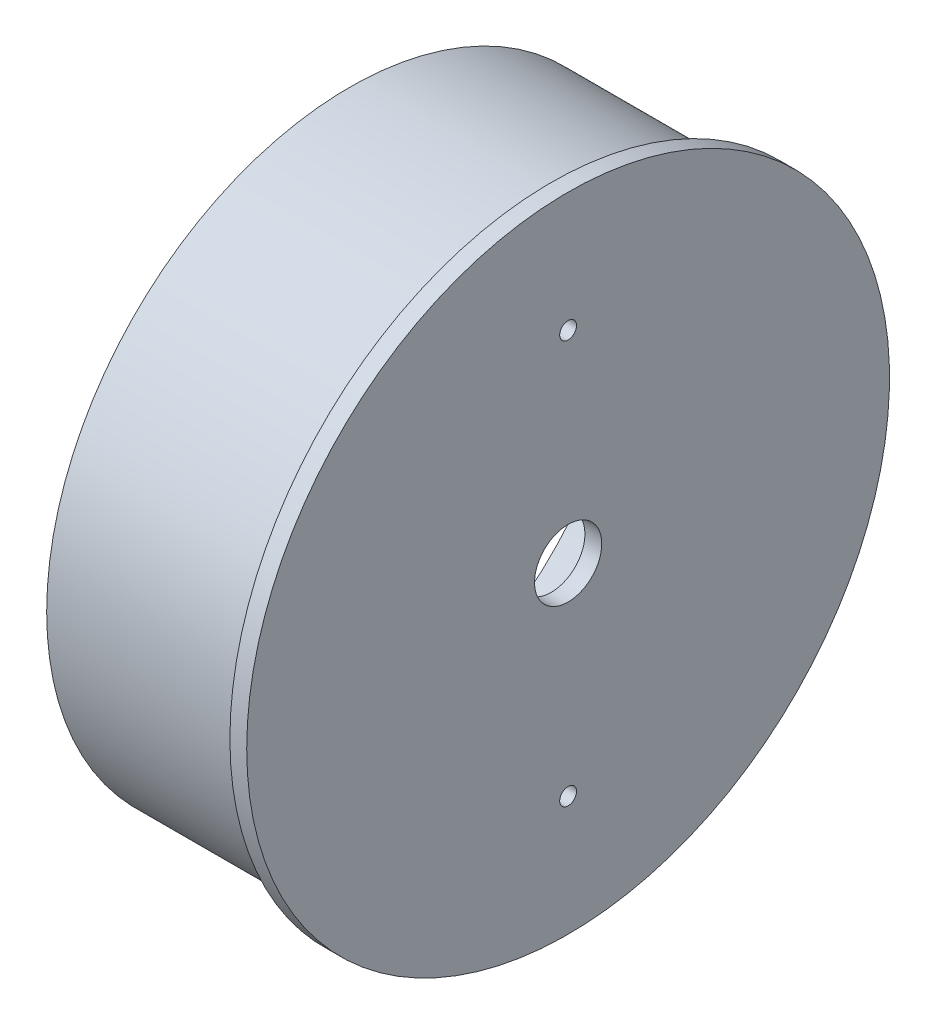
SolidWorks part; units mm, degrees
ref_plane "Front Plane" through (0, 0, 0) normal (0, 0, 1) x (1, 0, 0)
ref_plane "Top Plane" through (0, 0, 0) normal (0, 1, 0) x (1, 0, 0)
ref_plane "Right Plane" through (0, 0, 0) normal (1, 0, 0) x (0, 0, -1)
sketch "Sketch1" plane through (0, 0, 0) normal (0, 0, 1) x (1, 0, 0)
  line L1 (7.1264, 21.5516) -> (9.6264, 21.5516)
  line L2 (7.1264, 21.5516) -> (7.1264, -26.2484)
  line L3 (7.1264, -26.2484) -> (9.6264, -26.2484)
  line L4 (9.6264, 21.5516) -> (9.6264, -26.2484)
  line L5 (7.1264, 18.8016) -> (-22.8736, 18.8016)
  line L6 (7.1264, 18.8016) -> (7.1264, 16.3016)
  line L7 (7.1264, 16.3016) -> (-22.8736, 16.3016)
  line L8 (-22.8736, 18.8016) -> (-22.8736, 16.3016)
  dimension "D1" = 47.8
  dimension "D2" = 2.75
  dimension "D3" = 30
  dimension "D4" = 2.5
  dimension "D5" = 2.5
revolve "Revolve1" add sketch "Sketch1" angle 360 about L3 region at (8.3764, -2.3484, 0) region at (-7.8736, 17.5516, 0)
sketch "Sketch2" plane through (9.6264, 0, 0) normal (1, 0, 0) x (0, 0, -1)
  line L0 (0, 21.5516) -> (0, -74.0484)
  line L1 (0, -26.2484) -> (22.1708, -26.2484) construction
  circle A0 centre (0, -26.2484) radius 47.8 construction
  circle A1 centre (0, -26.2484) radius 5
  circle A2 centre (0, -56.2484) radius 1.25
  circle A3 centre (0, 3.7516) radius 1.25
  dimension "D1" = 2.5
  dimension "D2" = 30
extrude "Cut-Extrude1" cut sketch "Sketch2" against normal blind 10 contours L0 A1 | L0 L1 A1 | L1 L0 A1 | L0 A2 | L0 A2 | A3 L0 | A3 L0 region at (9.6264, 3.7516, -0.5305) region at (9.6264, -56.2484, -0.5305) region at (9.6264, -56.2484, 0.5305) region at (9.6264, -24.1263, -2.1221) region at (9.6264, -26.2484, 2.1221) region at (9.6264, 3.7516, 0.5305) region at (9.6264, -28.3705, -2.1221)
